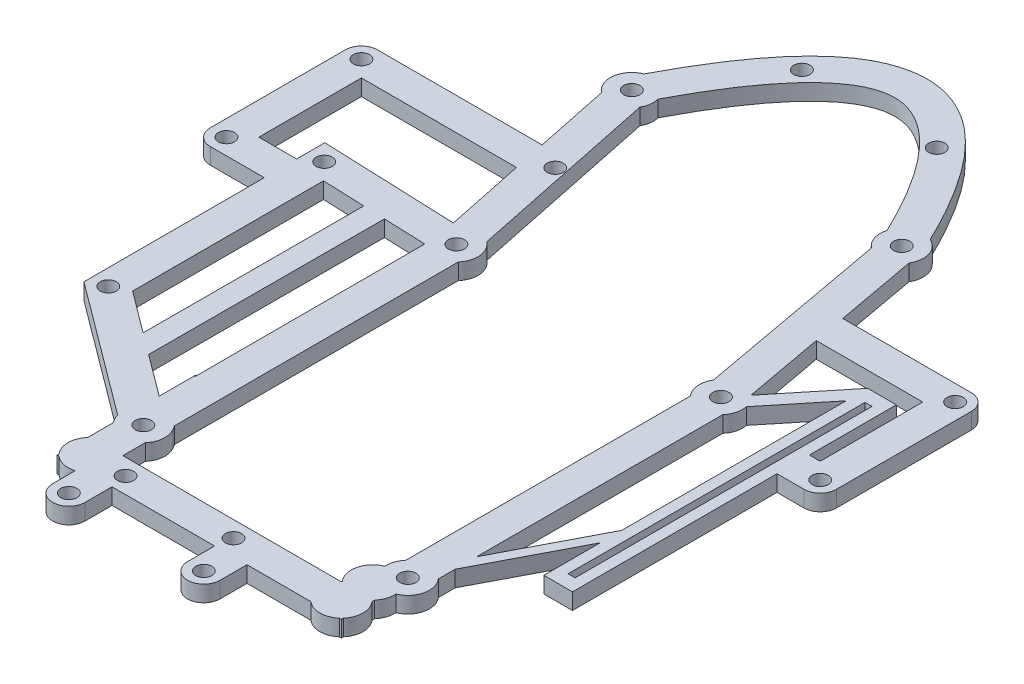
SolidWorks part; units mm, degrees
material "Thornel Mat VMA"
ref_plane "前视基准面" through (0, 0, 0) normal (0, 0, 1) x (1, 0, 0)
ref_plane "上视基准面" through (0, 0, 0) normal (0, 1, 0) x (1, 0, 0)
ref_plane "右视基准面" through (0, 0, 0) normal (1, 0, 0) x (0, 0, -1)
other "Configuration Table"
sketch "草图1" plane through (0, 0, 0) normal (0, 1, 0) x (1, 0, 0)
  line L0 (25, 0) -> (-25, 0) construction
  line L1 (0, 5) -> (0, 0) construction
  line L2 (-40, 5) -> (40, 5)
  line L3 (-40, 5) -> (-40, -115)
  line L4 (-40, -115) -> (40, -115)
  line L5 (40, 5) -> (40, -115)
  line L6 (0, 0) -> (0, -100) construction
  line L29 (-30, -91.2) -> (30, -91.2) construction
  line L34 (-30, -91.2) -> (-30, -108.8) construction
  line L35 (-30, -108.8) -> (30, -108.8) construction
  line L36 (30, -91.2) -> (30, -108.8) construction
  line L37 (-30, -91.2) -> (30, -108.8) construction
  line L38 (-30, -108.8) -> (30, -91.2) construction
  line L39 (-16.5, -41) -> (32.5, -41) construction
  line L40 (-16.5, -41) -> (-16.5, -99) construction
  line L41 (-16.5, -99) -> (32.5, -99) construction
  line L42 (32.5, -41) -> (32.5, -99) construction
  line L43 (-16.5, -41) -> (32.5, -99) construction
  line L44 (-16.5, -99) -> (32.5, -41) construction
  circle A0 centre (-25, 0) radius 1.5
  circle A1 centre (25, 0) radius 1.5
  circle A18 centre (-30, -91.2) radius 1.5
  circle A19 centre (-30, -108.8) radius 1.5
  circle A20 centre (30, -108.8) radius 1.5
  circle A21 centre (30, -91.2) radius 1.5
  circle A22 centre (-16.5, -41) radius 1.5
  circle A23 centre (-16.5, -99) radius 1.5
  circle A24 centre (32.5, -41) radius 1.5
  circle A25 centre (32.5, -99) radius 1.5
  point P3 (8, -70)
  point P4 (0, 0)
  point P14 (0, -100)
  point P17 (0, -100)
  point P23 (8, -70)
  point P32 (0, -100)
  dimension "D1" = 3
  dimension "D8" = 8
  dimension "D15" = 3
  dimension "D18" = 3
  dimension "D2" = 50
  dimension "D3" = 5
  dimension "D4" = 80
  dimension "D5" = 120
  dimension "D6" = 17.6
  dimension "D7" = 75
  dimension "D9" = 100
  dimension "D10" = 8
  dimension "D13" = 60
  dimension "D14" = 100
  dimension "D16" = 49
  dimension "D17" = 58
  dimension "D19" = 70
extrude "凸台-拉伸1" add sketch "草图1" along normal blind 3 contours A18 | A19 | L5 L2 L3 L4 A25 A24 A23 A22 A21 A20 A19 A18 A1 A0 | A21 | A20
sketch "草图2" plane through (0, 3, 0) normal (0, 1, 0) x (1, 0, 0)
  line L1 (40, -26) -> (50, -26)
  line L2 (40, -26) -> (40, -86)
  line L3 (40, -86) -> (50, -86)
  line L4 (50, -26) -> (50, -86)
  line L6 (-40, 5) -> (40, 5) construction
  line L7 (46.7, -28.5) -> (48, -28.5)
  line L8 (46.7, -28.5) -> (46.7, -83.5)
  line L9 (46.7, -83.5) -> (48, -83.5)
  line L10 (48, -28.5) -> (48, -83.5)
  dimension "D1" = 31
  dimension "D2" = 60
  dimension "D3" = 10
  dimension "D4" = 1.3
  dimension "D5" = 55
  dimension "D6" = 2.5
  dimension "D7" = 2
extrude "凸台-拉伸2" add sketch "草图2" against normal up to surface (3 mm away) contours L4 L1 L2 L3 L7 L10 L9 L8 up to face at (32.5, 0, 100.5)
sketch "草图6" plane through (0, 3, 0) normal (0, 1, 0) x (1, 0, 0)
  line L0 (-25, 0) -> (-16.5, -41) construction
  line L1 (-16.5, -41) -> (-16.5, -99) construction
  line L2 (-16.5, -99) -> (-16.6719, -98.661) construction
  line L3 (-16.6719, -98.661) -> (-16.6719, -108.8) construction
  line L4 (-16.6719, -108.8) -> (30, -108.8) construction
  line L5 (30, -108.8) -> (30, -102.9864) construction
  line L6 (30, -102.9864) -> (32.5, -99) construction
  line L7 (32.5, -99) -> (32.5, -41) construction
  line L8 (32.5, -41) -> (25, 0) construction
  line L9 (-27.9375, -0.609) -> (-19.5, -41.3077)
  line L10 (-19.5, -41.3077) -> (-19.5, -86.4493)
  line L11 (-19.5, -86.4493) -> (-19.6719, -86.1103)
  line L12 (-19.6719, -86.1103) -> (-19.6719, -111.8)
  line L13 (-19.6719, -111.8) -> (33, -111.8)
  line L14 (33, -111.8) -> (33, -103.8493)
  line L15 (33, -103.8493) -> (35.5, -99.8629)
  line L16 (35.5, -99.8629) -> (35.5, -40.7279)
  line L17 (35.5, -40.7279) -> (27.951, 0.5398)
  line L18 (-22.0625, 0.609) -> (-13.5, -40.6923)
  line L19 (-13.5, -40.6923) -> (-13.5, -105.8)
  line L20 (-13.5, -105.8) -> (-13.5, -105.8)
  line L21 (-13.5, -105.8) -> (-13.5, -105.8)
  line L22 (-13.5, -105.8) -> (27, -105.8)
  line L23 (27, -105.8) -> (27, -102.1235)
  line L24 (27, -102.1235) -> (29.5, -98.1371)
  line L25 (29.5, -98.1371) -> (29.5, -41.2721)
  line L26 (29.5, -41.2721) -> (22.049, -0.5398)
  line L27 (44.7, -26) -> (32.5, -41)
  line L28 (44.7, -75.572) -> (32.5, -99)
  line L29 (44.7, -26) -> (44.7, -86)
  line L33 (32.5, -45) -> (44.7, -30)
  line L34 (32.5, -95) -> (44.7, -71.572)
  circle A0 centre (-25, 0) radius 4
  circle A1 centre (-16.5, -41) radius 4
  circle A2 centre (-16.5, -99) radius 4
  circle A3 centre (-16.6719, -98.661) radius 4
  circle A4 centre (-16.6719, -108.8) radius 4
  circle A5 centre (30, -108.8) radius 4
  circle A6 centre (30, -102.9864) radius 4
  circle A7 centre (32.5, -99) radius 4
  circle A8 centre (32.5, -41) radius 4
  circle A9 centre (25, 0) radius 4
  dimension "D1" = 8
  dimension "D2" = 3
  dimension "D3" = 3
extrude "切除-拉伸1" cut sketch "草图6" against normal through all
sketch "草图8" plane through (0, 3, 0) normal (0, 1, 0) x (1, 0, 0)
  arc A1 (-21.5254, -1.9817) -> (-27.4004, -3.1997) centre (-25, 0) ccw construction
  arc A2 (-21.5254, -1.9817) -> (-27.4004, -3.1997) centre (-25, 0) ccw
  arc A3 (28.4271, -2.0627) -> (22.525, -3.1424) centre (25, 0) ccw construction
  arc A4 (28.4271, -2.0627) -> (22.525, -3.1424) centre (25, 0) ccw
  spline S0 degree 2 poles (-25, 0) (1.1461, 52.2755) (25, 0) knots 0 0 0 1 1 1 construction
  spline S1 degree 1 poles (-22.3169, -1.342) (22.2707, -1.2454) knots 0 0 1 1 construction
  spline S2 degree 2 poles (-22.3169, -1.342) (-17.4924, 8.2772) (-9.8667, 17.9338) (-4.9427, 21.6941) (-1.7859, 22.9093) (0.5765, 23.2138) (2.9116, 22.91) (5.9779, 21.7093) (10.6939, 17.9849) (17.8712, 8.3648) (22.2707, -1.2454) knots 0 0 0 0.1875 0.3125 0.40625 0.46875 0.53125 0.59375 0.6875 0.8125 1 1 1
  spline S3 degree 1 poles (-27.6831, 1.342) (27.7293, 1.2454) knots 0 0 1 1 construction
  spline S4 degree 2 poles (-27.6831, 1.342) (-22.7028, 11.3261) (-14.2558, 22.0897) (-8.0543, 26.9058) (-3.3314, 28.7536) (0.5741, 29.2659) (4.471, 28.7529) (9.1501, 26.8906) (15.1835, 22.0385) (23.1836, 11.2385) (27.7293, 1.2454) knots 0 0 0 0.1875 0.3125 0.40625 0.46875 0.53125 0.59375 0.6875 0.8125 1 1 1
  dimension "D1" = 3
  dimension "D2" = 3
extrude "凸台-拉伸4" add sketch "草图8" against normal up to surface (3 mm away) up to face at (10.4386, 0, 77.3572)
sketch "草图23" plane through (0, 3, 0) normal (0, 1, 0) x (1, 0, 0)
  line L0 (-16.5, -41) -> (-42, -40) construction
  line L1 (-42, -40) -> (-42, -80) construction
  line L2 (-42, -80) -> (-16.5, -99) construction
  line L3 (-16.3824, -38.0023) -> (-45, -36.88)
  line L4 (-45, -36.88) -> (-45, -81.5059)
  line L5 (-45, -81.5059) -> (-18.2924, -101.4056)
  line L6 (-16.6176, -43.9977) -> (-39, -43.12)
  line L7 (-39, -43.12) -> (-39, -78.4941)
  line L8 (-39, -78.4941) -> (-14.7076, -96.5944)
  line L26 (34.7937, -27.723) -> (28.538, -1.8661)
  line L30 (44.7, -26) -> (36.2012, -29.4831)
  line L31 (44.7, -75.572) -> (44.7, -86)
  line L33 (44.7, -75.572) -> (44.7, -86)
  line L34 (-27.1936, -3.3449) -> (-20.0928, -29.2417)
  line L35 (-19.5, -33.6458) -> (-19.5, -86.3542)
  line L36 (-19.5938, -86.4646) -> (-27.8712, -87.8135)
  line L37 (-33, -93.8458) -> (-33, -106.1542)
  line L38 (-33, -111.4458) -> (-33, -111.8)
  line L39 (-33, -111.8) -> (-32.6458, -111.8)
  line L40 (-27.3542, -111.8) -> (27.3542, -111.8)
  line L41 (32.6458, -111.8) -> (33, -111.8)
  line L42 (33, -111.8) -> (33, -111.4458)
  line L43 (33, -106.1542) -> (33, -93.8458)
  line L45 (36.3895, -88.0665) -> (40, -87.2)
  line L47 (40, -86) -> (50, -86)
  line L48 (50, -86) -> (50, -26)
  line L49 (50, -26) -> (44.7, -26)
  line L50 (44.7, -26) -> (36.2012, -29.4831)
  line L54 (-27.1936, -3.3449) -> (-20.0928, -29.2417)
  line L55 (-19.5, -33.6458) -> (-19.5, -86.3542)
  line L56 (-19.5938, -86.4646) -> (-27.8712, -87.8135)
  line L57 (-33, -93.8458) -> (-33, -106.1542)
  line L58 (-33, -111.4458) -> (-33, -111.8)
  line L59 (-33, -111.8) -> (-32.6458, -111.8)
  line L60 (-27.3542, -111.8) -> (27.3542, -111.8)
  line L61 (32.6458, -111.8) -> (33, -111.8)
  line L62 (33, -111.8) -> (33, -111.4458)
  line L63 (33, -106.1542) -> (33, -93.8458)
  line L65 (36.3895, -88.0665) -> (40, -87.2)
  line L67 (40, -86) -> (50, -86)
  line L68 (50, -86) -> (50, -26)
  line L69 (50, -26) -> (44.7, -26)
  line L71 (44.7, -86) -> (50, -86)
  line L72 (50, -86) -> (50, -26)
  line L73 (50, -26) -> (44.7, -26)
  line L74 (44.7, -26) -> (35.0239, -37.8968)
  line L75 (34.975, -37.8576) -> (28.4271, -2.0627)
  line L76 (-27.4004, -3.1997) -> (-19.9746, -39.0183)
  line L78 (-19.5, -43.6458) -> (-19.5, -86.4493)
  line L80 (-19.5, -86.4493) -> (-19.6719, -86.1103)
  line L82 (-19.6719, -86.1103) -> (-19.6719, -96.0153)
  line L84 (40, -87.2) -> (40, -86)
  line L85 (40, -87.2) -> (40, -86)
  line L86 (-19.6719, -101.4371) -> (-19.6719, -106.1542)
  line L88 (-19.6719, -111.4458) -> (-19.6719, -111.8)
  line L90 (-19.6719, -111.8) -> (-19.3176, -111.8)
  line L91 (-14.0261, -111.8) -> (27.3542, -111.8)
  line L92 (32.6458, -111.8) -> (33, -111.8)
  line L93 (33, -111.8) -> (33, -111.4458)
  line L94 (33, -106.1542) -> (33, -105.6321)
  line L95 (35.5, -96.3542) -> (35.5, -93.239)
  line L96 (35.5, -93.239) -> (44.7, -75.572)
  line L103 (44.7, -86) -> (50, -86)
  line L104 (50, -86) -> (50, -26)
  line L105 (50, -26) -> (44.7, -26)
  line L106 (44.7, -26) -> (35.0239, -37.8968)
  line L107 (34.975, -37.8576) -> (28.4271, -2.0627)
  line L108 (-27.4004, -3.1997) -> (-19.9746, -39.0183)
  line L109 (-19.5, -43.6458) -> (-19.5, -86.4493)
  line L110 (-19.5, -86.4493) -> (-19.6719, -86.1103)
  line L111 (-19.6719, -86.1103) -> (-19.6719, -96.0153)
  line L112 (-19.6719, -101.4371) -> (-19.6719, -106.1542)
  line L113 (-19.6719, -111.4458) -> (-19.6719, -111.8)
  line L114 (-19.6719, -111.8) -> (-19.3176, -111.8)
  line L115 (-14.0261, -111.8) -> (27.3542, -111.8)
  line L116 (32.6458, -111.8) -> (33, -111.8)
  line L117 (33, -111.8) -> (33, -111.4458)
  line L118 (33, -106.1542) -> (33, -105.6321)
  line L119 (35.5, -96.3542) -> (35.5, -93.239)
  line L120 (35.5, -93.239) -> (44.7, -75.572)
  circle A0 centre (-42, -40) radius 1.5
  circle A1 centre (-42, -80) radius 1.5
  arc A14 (28.538, -1.8661) -> (25.6345, 3.9494) centre (25, 0) ccw
  arc A15 (-25.6345, 3.9494) -> (-27.1936, -3.3449) centre (-25, 0) ccw
  arc A16 (-20.0928, -29.2417) -> (-19.5, -33.6458) centre (-16.5, -31) ccw
  arc A17 (-19.5, -86.3542) -> (-19.5938, -86.4646) centre (-16.5, -89) ccw
  arc A18 (-27.8712, -87.8135) -> (-33, -93.8458) centre (-30, -91.2) ccw
  arc A19 (-33, -106.1542) -> (-33, -111.4458) centre (-30, -108.8) ccw
  arc A20 (-32.6458, -111.8) -> (-27.3542, -111.8) centre (-30, -108.8) ccw
  arc A21 (27.3542, -111.8) -> (32.6458, -111.8) centre (30, -108.8) ccw
  arc A22 (33, -111.4458) -> (33, -106.1542) centre (30, -108.8) ccw
  arc A23 (33, -93.8458) -> (33.6527, -92.8303) centre (30, -91.2) ccw
  arc A25 (28.538, -1.8661) -> (25.6345, 3.9494) centre (25, 0) ccw
  arc A26 (-25.6345, 3.9494) -> (-27.1936, -3.3449) centre (-25, 0) ccw
  arc A27 (-20.0928, -29.2417) -> (-19.5, -33.6458) centre (-16.5, -31) ccw
  arc A28 (-19.5, -86.3542) -> (-19.5938, -86.4646) centre (-16.5, -89) ccw
  arc A29 (-27.8712, -87.8135) -> (-33, -93.8458) centre (-30, -91.2) ccw
  arc A30 (-33, -106.1542) -> (-33, -111.4458) centre (-30, -108.8) ccw
  arc A31 (-32.6458, -111.8) -> (-27.3542, -111.8) centre (-30, -108.8) ccw
  arc A32 (27.3542, -111.8) -> (32.6458, -111.8) centre (30, -108.8) ccw
  arc A33 (33, -111.4458) -> (33, -106.1542) centre (30, -108.8) ccw
  arc A34 (33, -93.8458) -> (33.6527, -92.8303) centre (30, -91.2) ccw
  arc A36 (35.0239, -37.8968) -> (34.975, -37.8576) centre (32.5, -41) ccw
  arc A37 (28.4271, -2.0627) -> (26.5997, 3.6662) centre (25, 0) ccw
  arc A38 (-26.4694, 3.7203) -> (-27.4004, -3.1997) centre (-25, 0) ccw
  arc A39 (-19.9746, -39.0183) -> (-19.5, -43.6458) centre (-16.5, -41) ccw
  arc A40 (-19.6719, -96.0153) -> (-20.1495, -100.6374) centre (-16.6719, -98.661) ccw
  arc A41 (-20.1495, -100.6374) -> (-19.6719, -101.4371) centre (-16.5, -99) ccw
  arc A42 (-19.6719, -106.1542) -> (-19.6719, -111.4458) centre (-16.6719, -108.8) ccw
  arc A43 (-19.3176, -111.8) -> (-14.0261, -111.8) centre (-16.6719, -108.8) ccw
  arc A44 (27.3542, -111.8) -> (32.6458, -111.8) centre (30, -108.8) ccw
  arc A46 (33, -111.4458) -> (33, -106.1542) centre (30, -108.8) ccw
  arc A48 (33, -105.6321) -> (33.9906, -102.7119) centre (30, -102.9864) ccw
  arc A50 (33.9906, -102.7119) -> (35.5, -96.3542) centre (32.5, -99) ccw
  arc A54 (33.6527, -92.8303) -> (36.3895, -88.0665) centre (32.5, -89) ccw
  arc A55 (33.6527, -92.8303) -> (36.3895, -88.0665) centre (32.5, -89) ccw
  arc A56 (36.2012, -29.4831) -> (34.7937, -27.723) centre (32.5, -31) ccw
  arc A57 (36.2012, -29.4831) -> (34.7937, -27.723) centre (32.5, -31) ccw
  arc A58 (35.0239, -37.8968) -> (34.975, -37.8576) centre (32.5, -41) ccw
  arc A60 (28.4271, -2.0627) -> (26.5997, 3.6662) centre (25, 0) ccw
  arc A62 (-26.4694, 3.7203) -> (-27.4004, -3.1997) centre (-25, 0) ccw
  arc A63 (-19.9746, -39.0183) -> (-19.5, -43.6458) centre (-16.5, -41) ccw
  arc A64 (-19.6719, -96.0153) -> (-20.1495, -100.6374) centre (-16.6719, -98.661) ccw
  arc A65 (-20.1495, -100.6374) -> (-19.6719, -101.4371) centre (-16.5, -99) ccw
  arc A66 (-19.6719, -106.1542) -> (-19.6719, -111.4458) centre (-16.6719, -108.8) ccw
  arc A67 (-19.3176, -111.8) -> (-14.0261, -111.8) centre (-16.6719, -108.8) ccw
  arc A68 (27.3542, -111.8) -> (32.6458, -111.8) centre (30, -108.8) ccw
  arc A69 (33, -111.4458) -> (33, -106.1542) centre (30, -108.8) ccw
  arc A70 (33, -105.6321) -> (33.9906, -102.7119) centre (30, -102.9864) ccw
  arc A71 (33.9906, -102.7119) -> (35.5, -96.3542) centre (32.5, -99) ccw
  spline S1 degree 2 poles (-4082.7157, -71823.4535) (927.524, -703.0054) (14.1246, 14.5454) (7.1758, 17.826) (0, 18.9571) (-7.1758, 17.826) (-14.1246, 14.5454) (-927.5327, -703.0122) (4082.8116, -71824.8147) knots -33.765999 -33.765999 -33.765999 0.1875 0.3125 0.4375 0.5625 0.6875 0.8125 34.766324 34.766324 34.766324 only from (25.6345, 3.9494) to (-25.6345, 3.9494)
  spline S2 degree 2 poles (25.6345, 3.9494) (21.616, 8.6603) (14.1246, 14.5454) (7.1758, 17.826) (0, 18.9571) (-7.1758, 17.826) (-14.1246, 14.5454) (-21.616, 8.6603) (-25.6345, 3.9494) knots 0.032999 0.032999 0.032999 0.1875 0.3125 0.4375 0.5625 0.6875 0.8125 0.967001 0.967001 0.967001
  spline S3 degree 2 poles (90.1394, -2993.0033) (150.3259, -160.4035) (15.1835, 22.0385) (9.1501, 26.8906) (4.471, 28.7529) (0.5741, 29.2659) (-3.3314, 28.7536) (-8.0543, 26.9058) (-14.2558, 22.0897) (-156.5887, -159.2786) (-229.5238, -2986.7882) knots -4.966885 -4.966885 -4.966885 0.187107 0.312107 0.405857 0.468357 0.530857 0.593357 0.687107 0.812107 5.952791 5.952791 5.952791 only from (26.5997, 3.6662) to (-26.4694, 3.7203)
  spline S4 degree 2 poles (26.5997, 3.6662) (22.5892, 12.0409) (15.1835, 22.0385) (9.1501, 26.8906) (4.471, 28.7529) (0.5741, 29.2659) (-3.3314, 28.7536) (-8.0543, 26.9058) (-14.2558, 22.0897) (-22.0858, 12.1122) (-26.4694, 3.7203) knots 0.022823 0.022823 0.022823 0.187107 0.312107 0.405857 0.468357 0.530857 0.593357 0.687107 0.812107 0.976784 0.976784 0.976784
  dimension "D3" = 3
  dimension "D4" = 3
  dimension "D5" = 0
  dimension "D1" = 3
  dimension "D2" = 3
  dimension "D6" = 0
extrude "凸台-拉伸9" add sketch "草图23" against normal up to surface (3 mm away) contours A28 L55 L8 L7 L6 A27 L54 L3 L4 L5 L56 A1 A0 | A64 L111 L8 L56 A29 L5
sketch "草图25" plane through (0, 3, 0) normal (0, 1, 0) x (1, 0, 0)
  line L0 (0, -111.8) -> (0, -105.8) construction
  line L1 (-27.3542, -111.8) -> (27.3542, -111.8) construction
  line L2 (-14, -105.8) -> (14, -105.8) construction
  line L3 (10, -108.8) -> (-10, -108.8) construction
  circle A0 centre (-10, -108.8) radius 1.5
  circle A1 centre (10, -108.8) radius 1.5
  point P9 (0, -108.8)
  dimension "D1" = 3
  dimension "D2" = 20
extrude "切除-拉伸8" cut sketch "草图25" against normal through all
sketch "草图26" plane through (0, 3, 0) normal (0, 1, 0) x (1, 0, 0)
  line L0 (-22.6804, -19.8046) -> (-16.5901, -19.3265) construction
  line L1 (-27.1936, -3.3449) -> (-20.4333, -28) construction
  line L2 (-21.4072, -1.7583) -> (-14.3064, -27.6551) construction
  circle A0 centre (-19.6353, -19.5656) radius 1.5
  circle A1 centre (17.9459, 7.8265) radius 1.5
  dimension "D1" = 3
  dimension "D2" = 3
extrude "切除-拉伸9" cut sketch "草图26" against normal through all contours A0 L0 | L0 A0 | A1
sketch "草图27" plane through (0, 3, 0) normal (0, 1, 0) x (1, 0, 0)
  line L0 (-29.25, -43.5023) -> (-29.3359, -85.6948) construction
  line L1 (-19.5, -43.8847) -> (-39, -43.12) construction
  line L2 (-39, -78.4941) -> (-19.6719, -92.8955) construction
  line L3 (-31.2376, -37.4197) -> (-31.3359, -85.6907)
  line L4 (-27.25, -43.5064) -> (-27.3542, -94.6538)
  line L5 (-27.25, -43.5064) -> (-27.3359, -85.6988) construction
  line L6 (-31.25, -43.4982) -> (-31.3359, -85.6907) construction
  line L7 (-39, -43.12) -> (-19.5, -43.8847) construction
  line L8 (-39, -43.12) -> (-19.5, -43.8847)
  line L9 (-19.6719, -92.8955) -> (-39, -78.4941) construction
  line L10 (-19.6719, -92.8955) -> (-39, -78.4941)
  line L29 (44.7, -75.572) -> (44.7, -86)
  line L30 (44.7, -86) -> (50, -86)
  line L31 (50, -86) -> (50, -26)
  line L32 (50, -26) -> (44.7, -26)
  line L33 (44.7, -26) -> (35.0239, -37.8968)
  line L34 (34.975, -37.8576) -> (28.4271, -2.0627)
  line L35 (-27.4004, -3.1997) -> (-20.2164, -37.852)
  line L36 (-20.2164, -37.852) -> (-45, -36.88)
  line L37 (-45, -36.88) -> (-45, -81.5059)
  line L38 (-45, -81.5059) -> (-20.5225, -99.7441)
  line L39 (-19.6719, -101.4371) -> (-19.6719, -106.1542)
  line L40 (-19.6719, -111.4458) -> (-19.6719, -111.8)
  line L41 (-19.6719, -111.8) -> (-19.3176, -111.8)
  line L42 (-14.0261, -111.8) -> (27.3542, -111.8)
  line L43 (32.6458, -111.8) -> (33, -111.8)
  line L44 (33, -111.8) -> (33, -111.4458)
  line L45 (33, -106.1542) -> (33, -105.6321)
  line L46 (35.5, -96.3542) -> (35.5, -93.239)
  line L47 (35.5, -93.239) -> (44.7, -75.572)
  line L48 (44.7, -75.572) -> (44.7, -86)
  line L54 (44.7, -86) -> (50, -86)
  line L55 (50, -86) -> (50, -26)
  line L56 (50, -26) -> (44.7, -26)
  line L57 (44.7, -26) -> (35.0239, -37.8968)
  line L58 (34.975, -37.8576) -> (28.4271, -2.0627)
  line L59 (-27.4004, -3.1997) -> (-20.2164, -37.852)
  line L60 (-20.2164, -37.852) -> (-45, -36.88)
  line L61 (-45, -36.88) -> (-45, -81.5059)
  line L62 (-45, -81.5059) -> (-20.5225, -99.7441)
  line L63 (-19.6719, -101.4371) -> (-19.6719, -106.1542)
  line L64 (-19.6719, -111.4458) -> (-19.6719, -111.8)
  line L65 (-19.6719, -111.8) -> (-19.3176, -111.8)
  line L66 (-14.0261, -111.8) -> (27.3542, -111.8)
  line L67 (32.6458, -111.8) -> (33, -111.8)
  line L68 (33, -111.8) -> (33, -111.4458)
  line L69 (33, -106.1542) -> (33, -105.6321)
  line L70 (35.5, -96.3542) -> (35.5, -93.239)
  line L71 (35.5, -93.239) -> (44.7, -75.572)
  arc A12 (35.0239, -37.8968) -> (34.975, -37.8576) centre (32.5, -41) ccw
  arc A13 (28.4271, -2.0627) -> (26.5997, 3.6662) centre (25, 0) ccw
  arc A14 (-26.4694, 3.7203) -> (-27.4004, -3.1997) centre (-25, 0) ccw
  arc A15 (-20.5225, -99.7441) -> (-20.1495, -100.6374) centre (-16.6719, -98.661) ccw
  arc A16 (-20.1495, -100.6374) -> (-19.6719, -101.4371) centre (-16.5, -99) ccw
  arc A17 (-19.6719, -106.1542) -> (-19.6719, -111.4458) centre (-16.6719, -108.8) ccw
  arc A18 (-19.3176, -111.8) -> (-14.0261, -111.8) centre (-16.6719, -108.8) ccw
  arc A19 (27.3542, -111.8) -> (32.6458, -111.8) centre (30, -108.8) ccw
  arc A20 (33, -111.4458) -> (33, -106.1542) centre (30, -108.8) ccw
  arc A21 (33, -105.6321) -> (33.9906, -102.7119) centre (30, -102.9864) ccw
  arc A22 (33.9906, -102.7119) -> (35.5, -96.3542) centre (32.5, -99) ccw
  arc A24 (35.0239, -37.8968) -> (34.975, -37.8576) centre (32.5, -41) ccw
  arc A25 (28.4271, -2.0627) -> (26.5997, 3.6662) centre (25, 0) ccw
  arc A26 (-26.4694, 3.7203) -> (-27.4004, -3.1997) centre (-25, 0) ccw
  arc A27 (-20.5225, -99.7441) -> (-20.1495, -100.6374) centre (-16.6719, -98.661) ccw
  arc A28 (-20.1495, -100.6374) -> (-19.6719, -101.4371) centre (-16.5, -99) ccw
  arc A29 (-19.6719, -106.1542) -> (-19.6719, -111.4458) centre (-16.6719, -108.8) ccw
  arc A30 (-19.3176, -111.8) -> (-14.0261, -111.8) centre (-16.6719, -108.8) ccw
  arc A31 (27.3542, -111.8) -> (32.6458, -111.8) centre (30, -108.8) ccw
  arc A32 (33, -111.4458) -> (33, -106.1542) centre (30, -108.8) ccw
  arc A33 (33, -105.6321) -> (33.9906, -102.7119) centre (30, -102.9864) ccw
  arc A34 (33.9906, -102.7119) -> (35.5, -96.3542) centre (32.5, -99) ccw
  spline S1 degree 2 poles (90.1394, -2993.0033) (150.3259, -160.4035) (15.1835, 22.0385) (9.1501, 26.8906) (4.471, 28.7529) (0.5741, 29.2659) (-3.3314, 28.7536) (-8.0543, 26.9058) (-14.2558, 22.0897) (-156.5887, -159.2786) (-229.5238, -2986.7882) knots -4.966885 -4.966885 -4.966885 0.187107 0.312107 0.405857 0.468357 0.530857 0.593357 0.687107 0.812107 5.952791 5.952791 5.952791 only from (26.5997, 3.6662) to (-26.4694, 3.7203)
  spline S2 degree 2 poles (26.5997, 3.6662) (22.5892, 12.0409) (15.1835, 22.0385) (9.1501, 26.8906) (4.471, 28.7529) (0.5741, 29.2659) (-3.3314, 28.7536) (-8.0543, 26.9058) (-14.2558, 22.0897) (-22.0858, 12.1122) (-26.4694, 3.7203) knots 0.022823 0.022823 0.022823 0.187107 0.312107 0.405857 0.468357 0.530857 0.593357 0.687107 0.812107 0.976784 0.976784 0.976784
  dimension "D1" = 2
  dimension "D2" = 2
  dimension "D3" = 0
extrude "凸台-拉伸10" add sketch "草图27" against normal up to surface (3 mm away) contours L10 L4 L8 L3 up to face at (-19.6353, 0, 21.0656)
sketch "草图28" plane through (0, 3, 0) normal (0, 1, 0) x (1, 0, 0)
  line L0 (0, 0) -> (0, 19) construction
  line L1 (12.5, 19) -> (-12.5, 19) construction
  circle A0 centre (-12.5, 19) radius 1.5
  circle A1 centre (12.5, 19) radius 1.5
  point P6 (0, 19)
  point P8 (0, 19.6556)
  dimension "D1" = 3
  dimension "D2" = 25
  dimension "D3" = 19
extrude "切除-拉伸10" cut sketch "草图28" against normal through all
sketch "草图29" plane through (0, 3, 0) normal (0, 1, 0) x (1, 0, 0)
  line L0 (0, 0) -> (0, -86.6413) construction
  line L1 (-55, -20.1037) -> (-55, -45.1037) construction
  line L2 (55, -32.6037) -> (-55, -32.6037) construction
  line L3 (55, -20.1037) -> (55, -45.1037) construction
  line L4 (-55, -20.1037) -> (-23.896, -20.1037) construction
  line L5 (-45, -36.88) -> (-45, -81.5059) construction
  line L6 (-55, -45.1037) -> (-45, -45.1037) construction
  line L7 (55, -20.1037) -> (31.7273, -20.1037) construction
  line L8 (50, -26) -> (50, -86) construction
  line L9 (55, -45.1037) -> (50, -45.1037) construction
  line L10 (-45, -42.1037) -> (-45, -81.5059)
  line L11 (50, -26) -> (50, -86)
  line L12 (-55, -20.1037) -> (-55, -45.1037) construction
  line L13 (55, -20.1037) -> (55, -45.1037) construction
  line L14 (-52, -42.1037) -> (-45, -42.1037)
  line L15 (-52, -23.1037) -> (-52, -42.1037)
  line L16 (-52, -23.1037) -> (-23.274, -23.1037)
  line L17 (52, -23.1037) -> (32.2761, -23.1037)
  line L18 (52, -23.1037) -> (52, -42.1037)
  line L19 (52, -42.1037) -> (50, -42.1037)
  line L20 (-58, -48.1037) -> (-45, -48.1037)
  line L21 (-58, -17.1037) -> (-58, -48.1037)
  line L22 (-58, -17.1037) -> (-24.5179, -17.1037)
  line L23 (58, -17.1037) -> (31.1785, -17.1037)
  line L24 (58, -17.1037) -> (58, -48.1037)
  line L25 (58, -48.1037) -> (50, -48.1037)
  line L26 (55, -20.1037) -> (50, -20.1037) construction
  line L27 (34.975, -37.8576) -> (28.4271, -2.0627) construction
  line L28 (52, -23.1037) -> (50, -23.1037) construction
  line L29 (58, -17.1037) -> (50, -17.1037) construction
  line L30 (-58, -17.1037) -> (-45, -17.1037) construction
  line L31 (-55, -20.1037) -> (-45, -20.1037) construction
  line L32 (-27.4004, -3.1997) -> (-20.2164, -37.852) construction
  line L33 (-52, -23.1037) -> (-45, -23.1037) construction
  line L34 (-52, -42.1037) -> (-45, -42.1037) construction
  line L35 (-58, -48.1037) -> (-45, -48.1037) construction
  line L36 (-27.4004, -3.1997) -> (-20.2164, -37.852)
  line L37 (34.975, -37.8576) -> (28.4271, -2.0627)
  circle A0 centre (-55, -20.1037) radius 1.5
  circle A1 centre (-55, -45.1037) radius 1.5
  circle A2 centre (55, -45.1037) radius 1.5
  circle A3 centre (55, -20.1037) radius 1.5
  circle A4 centre (-55, -20.1037) radius 3
  circle A5 centre (-55, -45.1037) radius 3
  circle A6 centre (55, -20.1037) radius 3
  circle A7 centre (55, -45.1037) radius 3
  point P6 (-55, -32.6037)
  point P9 (0, -32.6037)
  point P12 (55, -32.6037)
  point P29 (-45, -42.88)
  point P44 (0, -16.0698)
  point P45 (0, -18.7546)
  point P46 (50, -6.4813)
  point P48 (50, -4.7554)
  point P49 (0, 0)
  point P50 (29.0188, -5.2971)
  point P53 (0, 0)
  point P54 (29.5002, -7.9287)
  point P56 (28.6577, -3.3233)
  point P58 (-41.0301, -3.5207)
  point P60 (-45, -6.9419)
  point P62 (-27.2248, -4.0471)
  point P65 (-26.4064, -7.9945)
  point P66 (-25.6426, -11.6788)
  point P68 (-22.069, -28.9161)
  point P70 (-21.0324, -33.9162)
  point P72 (0, -19.3106)
  point P73 (-55, -28.7267)
  point P74 (-20.2164, -34.5231)
  point P75 (-45, -38.5)
  point P76 (0, 0)
  point P77 (0, 0)
  point P78 (0, 0)
  dimension "D2" = 3
  dimension "D3" = 6
  dimension "D1" = 25
  dimension "D4" = 110
  dimension "D5" = 3
  dimension "D6" = 3
extrude "凸台-拉伸11" add sketch "草图29" against normal up to surface (3 mm away) contours A5 L20 L10 L14 L15 L16 L22 A4 L21 | A4 A0 | A5 A1 | A7 L24 A6 L23 L11 L17 L18 L19 L25 | A6 A3 | A7 A2
sketch "草图30" plane through (0, 3, 0) normal (0, 1, 0) x (1, 0, 0)
  line L0 (0, 0) -> (0, -116.8) construction
  line L1 (12.5, -116.8) -> (-12.5, -116.8) construction
  line L2 (-12.5, -116.8) -> (-12.5, -111.8) construction
  line L3 (-14.0261, -111.8) -> (27.3542, -111.8) construction
  line L4 (12.5, -116.8) -> (12.5, -111.8) construction
  line L5 (-9.5, -116.8) -> (-9.5, -111.8)
  line L6 (15.5, -116.8) -> (15.5, -111.8)
  line L7 (-15.5, -116.8) -> (-15.5, -111.8)
  line L8 (9.5, -116.8) -> (9.5, -111.8)
  line L9 (-14.0261, -111.8) -> (27.3542, -111.8)
  circle A0 centre (-12.5, -116.8) radius 1.5
  circle A1 centre (12.5, -116.8) radius 1.5
  circle A2 centre (-12.5, -116.8) radius 3
  circle A3 centre (12.5, -116.8) radius 3
  arc A4 (-19.3176, -111.8) -> (-14.0261, -111.8) centre (-16.6719, -108.8) ccw construction
  arc A5 (-19.3176, -111.8) -> (-14.0261, -111.8) centre (-16.6719, -108.8) ccw
  point P6 (0, -116.8)
  dimension "D2" = 3
  dimension "D3" = 6
  dimension "D1" = 25
  dimension "D6" = 5
  dimension "D4" = 3
  dimension "D5" = 3
extrude "凸台-拉伸12" add sketch "草图30" against normal up to surface (3 mm away) contours A5 L7 A2 L5 L9 | A2 A0 | A3 L6 L9 L8 | A3 A1 up to face at (43.8719, 0, 32.2711)
